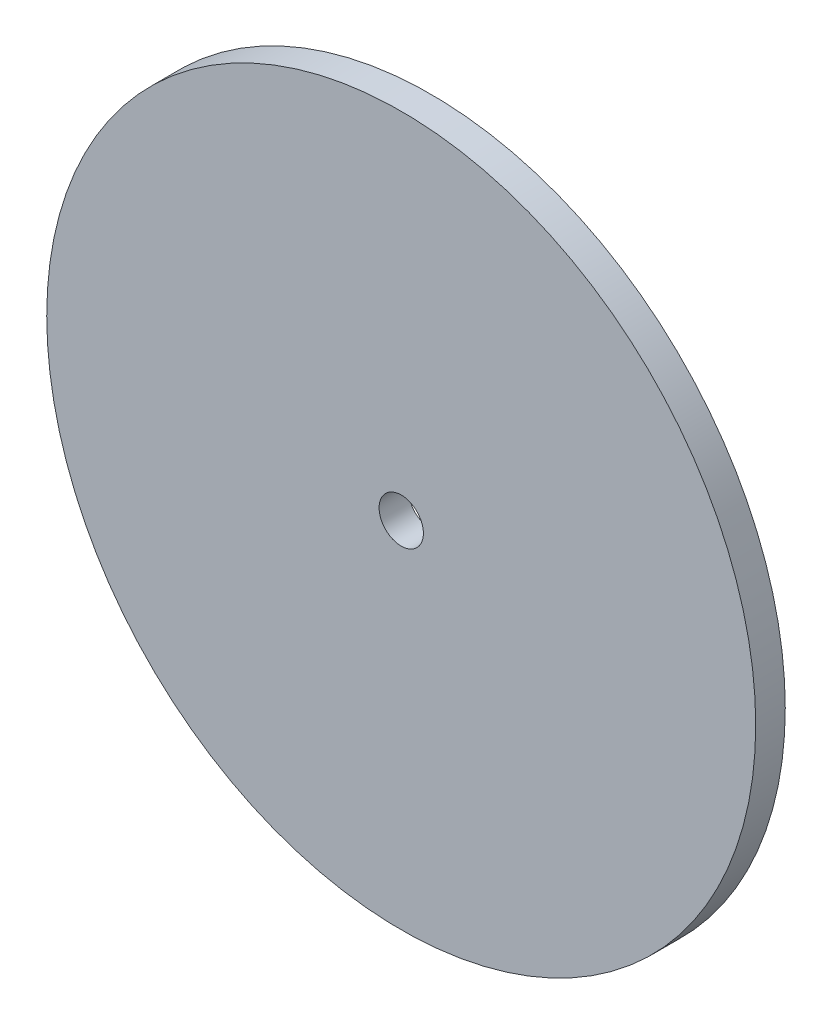
SolidWorks part; units mm, degrees
ref_plane "Front Plane" through (0, 0, 0) normal (0, 0, 1) x (1, 0, 0)
ref_plane "Top Plane" through (0, 0, 0) normal (0, 1, 0) x (1, 0, 0)
ref_plane "Right Plane" through (0, 0, 0) normal (1, 0, 0) x (0, 0, -1)
sketch "Sketch1" plane through (0, 0, 0) normal (0, 0, 1) x (1, 0, 0)
  circle A1 centre (0, 0) radius 76.2
  circle A2 centre (0, 0) radius 4.7625
  dimension "D1" = 9.525
  dimension "D2" = 152.4
extrude "Boss-Extrude1" add sketch "Sketch1" along normal blind 6.35 contours A1
extrude "Cut-Extrude3" cut sketch "Sketch1<4>" against normal through all and the other way through all contours A2
sketch "Sketch1<4>" plane through (0, 0, 0) normal (0, 0, 1) x (1, 0, 0) same geometry as "Sketch1"
sketch "Sketch2" plane through (0, 0, 0) normal (0, 0, -1) x (-1, 0, 0)
  line L0 (0, 63.5) -> (0, 0) construction
  line L2 (0, 0) -> (0, -63.5) construction
  circle A0 centre (0, 63.5) radius 3.175
  circle A1 centre (0, -63.5) radius 3.175
  dimension "D1" = 6.35
  dimension "D2" = 63.5
  dimension "D4" = 6.35
  dimension "D3" = 63.5
extrude "Cut-Extrude4" cut sketch "Sketch2" against normal blind 3.175 contours A1 | A0
